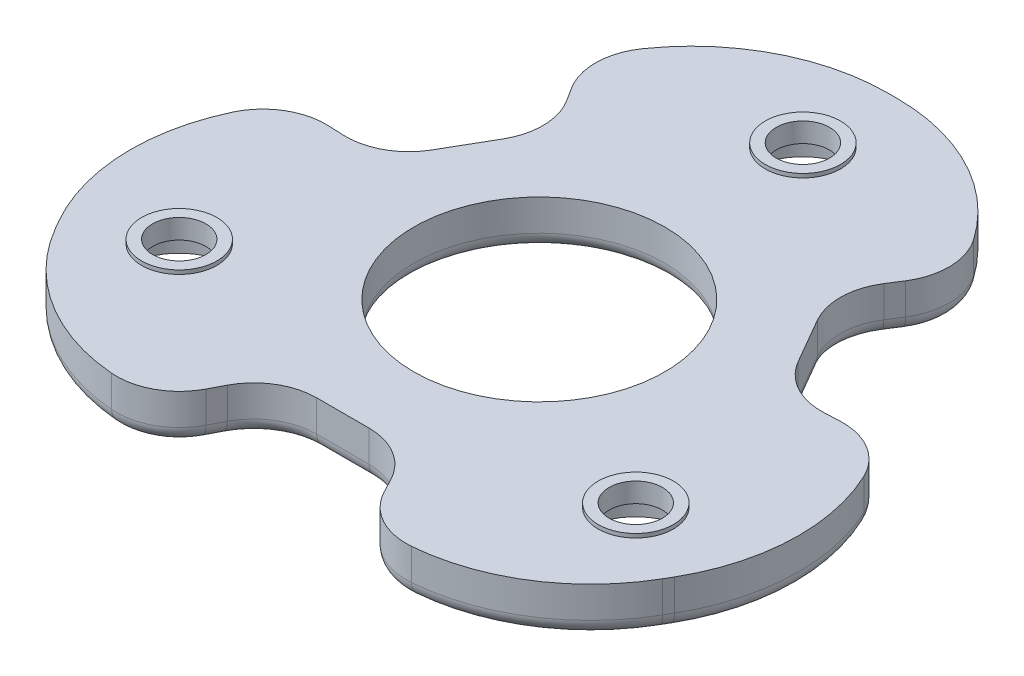
SolidWorks part; units mm, degrees
ref_plane "Front Plane" through (0, 0, 0) normal (0, 0, 1) x (1, 0, 0)
ref_plane "Top Plane" through (0, 0, 0) normal (0, 1, 0) x (1, 0, 0)
ref_plane "Right Plane" through (0, 0, 0) normal (1, 0, 0) x (0, 0, -1)
sketch "Sketch2" plane through (0, 0, 0) normal (0, 1, 0) x (1, 0, 0)
  line L0 (-0.2831, 22.5) -> (0.2831, 22.5)
  line L1 (11.1084, 16.25) -> (11.961, 14.7733)
  line L2 (19.6271, -11.0048) -> (19.344, -11.4952)
  line L3 (8.5187, -17.7452) -> (6.8136, -17.7452)
  line L4 (-19.344, -11.4952) -> (-19.6271, -11.0048)
  line L5 (-19.6271, 1.4952) -> (-18.7746, 2.9719)
  line L6 (-19.4856, -11.25) -> (0, 0) construction
  line L7 (0, 0) -> (0, 22.5) construction
  line L8 (0, 0) -> (19.4856, -11.25) construction
  line L9 (-11.961, 14.7733) -> (-8.8018, 9.8052)
  line L10 (-12.8925, 2.72) -> (-8.8018, 9.8052)
  line L11 (-12.8925, 2.72) -> (-18.7746, 2.9719)
  line L12 (-15.3678, 8.8726) -> (0, 0) construction
  line L13 (-15.8335, 2.8459) -> (-10.3814, 12.2893) construction
  line L14 (-11.961, 14.7733) -> (-11.1084, 16.25)
  line L15 (18.7746, 2.9719) -> (12.8925, 2.72)
  line L16 (8.8018, 9.8052) -> (12.8925, 2.72)
  line L17 (8.8018, 9.8052) -> (11.961, 14.7733)
  line L18 (-6.8136, -17.7452) -> (-4.0907, -12.5252)
  line L19 (4.0907, -12.5252) -> (-4.0907, -12.5252)
  line L20 (4.0907, -12.5252) -> (6.8136, -17.7452)
  line L21 (18.7746, 2.9719) -> (19.6271, 1.4952)
  line L22 (-6.8136, -17.7452) -> (-8.5187, -17.7452)
  circle A0 centre (0, 0) radius 8.4 construction
  circle A1 centre (0, 16.8) radius 8.4 construction
  circle A2 centre (0, 0) radius 24.8 construction
  circle A3 centre (0, 16.8) radius 1.7
  circle A4 centre (14.5492, -8.4) radius 1.7
  circle A5 centre (-14.5492, -8.4) radius 1.7
  arc A6 (19.6271, 1.4952) -> (19.6271, -11.0048) centre (8.8018, -4.7548) cw
  arc A7 (19.344, -11.4952) -> (8.5187, -17.7452) centre (8.5187, -5.2452) cw
  arc A8 (-8.5187, -17.7452) -> (-19.344, -11.4952) centre (-8.5187, -5.2452) cw
  arc A9 (-19.6271, -11.0048) -> (-19.6271, 1.4952) centre (-8.8018, -4.7548) cw
  arc A10 (0.2831, 22.5) -> (11.1084, 16.25) centre (0.2831, 10) cw
  arc A11 (-0.2831, 22.5) -> (-11.1084, 16.25) centre (-0.2831, 10) ccw
  circle A12 centre (0, 0) radius 8
  point P14 (0, 0)
  point P32 (7.5, 22.5)
  point P35 (-7.5, 22.5)
  point P42 (-13.1075, 7.5676)
  point P55 (0, 0)
  point P62 (0, 0)
  dimension "D1" = 16.8
  dimension "D2" = 16.8
  dimension "D3" = 49.6
  dimension "D4" = 3.4
  dimension "D9" = 12.5
  dimension "D10" = 16
  dimension "D6" = 120
  dimension "D7" = 15
  dimension "D8" = 22.5
  dimension "D11" = 3
  dimension "D5" = 3
extrude "Boss-Extrude1" add sketch "Sketch2" along normal blind 1
sketch "Sketch3" plane through (0, 0, 0) normal (0, -1, 0) x (1, 0, 0)
  line L6 (19.6271, 11.0048) -> (19.344, 11.4952)
  line L7 (8.5187, 17.7452) -> (6.8136, 17.7452)
  line L8 (-19.344, 11.4952) -> (-19.6271, 11.0048)
  line L9 (-19.6271, -1.4952) -> (-18.7746, -2.9719)
  line L10 (-0.2831, -22.5) -> (0.2831, -22.5)
  line L11 (11.1084, -16.25) -> (11.961, -14.7733)
  line L12 (19.6271, 11.0048) -> (19.344, 11.4952)
  line L13 (8.5187, 17.7452) -> (6.8136, 17.7452)
  line L14 (-19.344, 11.4952) -> (-19.6271, 11.0048)
  line L15 (-19.6271, -1.4952) -> (-18.7746, -2.9719)
  line L16 (-0.2831, -22.5) -> (0.2831, -22.5)
  line L17 (11.1084, -16.25) -> (11.961, -14.7733)
  line L30 (-11.961, -14.7733) -> (-11.1084, -16.25)
  line L31 (-11.961, -14.7733) -> (-11.1084, -16.25)
  line L32 (11.961, -14.7733) -> (8.8018, -9.8052)
  line L33 (11.961, -14.7733) -> (8.8018, -9.8052)
  line L34 (8.8018, -9.8052) -> (12.8925, -2.72)
  line L35 (8.8018, -9.8052) -> (12.8925, -2.72)
  line L36 (12.8925, -2.72) -> (18.7746, -2.9719)
  line L37 (12.8925, -2.72) -> (18.7746, -2.9719)
  line L38 (18.7746, -2.9719) -> (19.6271, -1.4952)
  line L39 (18.7746, -2.9719) -> (19.6271, -1.4952)
  line L40 (6.8136, 17.7452) -> (4.0907, 12.5252)
  line L41 (6.8136, 17.7452) -> (4.0907, 12.5252)
  line L42 (4.0907, 12.5252) -> (-4.0907, 12.5252)
  line L43 (4.0907, 12.5252) -> (-4.0907, 12.5252)
  line L44 (-4.0907, 12.5252) -> (-6.8136, 17.7452)
  line L45 (-4.0907, 12.5252) -> (-6.8136, 17.7452)
  line L46 (-6.8136, 17.7452) -> (-8.5187, 17.7452)
  line L47 (-6.8136, 17.7452) -> (-8.5187, 17.7452)
  line L48 (-18.7746, -2.9719) -> (-12.8925, -2.72)
  line L49 (-18.7746, -2.9719) -> (-12.8925, -2.72)
  line L50 (-12.8925, -2.72) -> (-8.8018, -9.8052)
  line L51 (-12.8925, -2.72) -> (-8.8018, -9.8052)
  line L52 (-8.8018, -9.8052) -> (-11.961, -14.7733)
  line L53 (-8.8018, -9.8052) -> (-11.961, -14.7733)
  circle A0 centre (-14.5492, 8.4) radius 3.5
  circle A1 centre (0, -16.8) radius 3.5
  circle A2 centre (14.5492, 8.4) radius 3.5
  circle A3 centre (0, 0) radius 8 construction
  circle A4 centre (0, 0) radius 8
  arc A6 (19.6271, -1.4952) -> (19.6271, 11.0048) centre (8.8018, 4.7548) ccw
  arc A7 (19.344, 11.4952) -> (8.5187, 17.7452) centre (8.5187, 5.2452) ccw
  arc A8 (-8.5187, 17.7452) -> (-19.344, 11.4952) centre (-8.5187, 5.2452) ccw
  arc A9 (-19.6271, 11.0048) -> (-19.6271, -1.4952) centre (-8.8018, 4.7548) ccw
  arc A10 (-11.1084, -16.25) -> (-0.2831, -22.5) centre (-0.2831, -10) ccw
  arc A11 (0.2831, -22.5) -> (11.1084, -16.25) centre (0.2831, -10) ccw
  arc A12 (19.6271, -1.4952) -> (19.6271, 11.0048) centre (8.8018, 4.7548) ccw
  arc A13 (19.344, 11.4952) -> (8.5187, 17.7452) centre (8.5187, 5.2452) ccw
  arc A14 (-8.5187, 17.7452) -> (-19.344, 11.4952) centre (-8.5187, 5.2452) ccw
  arc A15 (-19.6271, 11.0048) -> (-19.6271, -1.4952) centre (-8.8018, 4.7548) ccw
  arc A16 (-11.1084, -16.25) -> (-0.2831, -22.5) centre (-0.2831, -10) ccw
  arc A17 (0.2831, -22.5) -> (11.1084, -16.25) centre (0.2831, -10) ccw
  dimension "D2" = 7
  dimension "D1" = 0
extrude "Boss-Extrude2" add sketch "Sketch3" along normal blind 2
fillet "Fillet1" radius 4 12 edges at (-11.961, -0.5, -14.7733) (-8.8018, -0.5, -9.8052) (-18.7746, -0.5, -2.9719) (-12.8925, -0.5, -2.72) (-6.8136, -0.5, 17.7452) (-4.0907, -0.5, 12.5252) (6.8136, -0.5, 17.7452) (4.0907, -0.5, 12.5252) (18.7746, -0.5, -2.9719) (12.8925, -0.5, -2.72) (8.8018, -0.5, -9.8052) (11.961, -0.5, -14.7733)
fillet "Fillet2" radius 1 31 edges at (18.5592, -2, -2.2936) (15.817, -2, -2.8452) (13.2187, -2, -3.314) (10.8471, -2, -6.2626) (9.4793, -2, -9.7907) (10.3726, -2, -12.2753) (11.2659, -2, -14.9259) (6.0787, -2, -21.0753) (0, -2, -22.5) (-6.0787, -2, -21.0753) (-11.2659, -2, -14.9259) (-10.3726, -2, -12.2753) (-9.4793, -2, -9.7907) (-10.8471, -2, -6.2626) (-13.2187, -2, -3.314) (-15.817, -2, -2.8452) (-18.5592, -2, -2.2936) (-21.2911, -2, 5.2733) (-19.4856, -2, 11.25) (-15.2124, -2, 15.8019) (-7.2933, -2, 17.2195) (-5.4445, -2, 15.1206) (-3.7393, -2, 13.1047) (0, -2, 12.5252) (3.7393, -2, 13.1047) (5.4445, -2, 15.1206) (7.2933, -2, 17.2195) (15.2124, -2, 15.8019) (19.4856, -2, 11.25) (0, -2, -8) (21.2911, -2, 5.2733)
sketch "Sketch4" plane through (0, 1, 0) normal (0, 1, 0) x (1, 0, 0)
  circle A0 centre (0, 16.8) radius 2.4
  circle A1 centre (0, 16.8) radius 1.7 construction
  circle A2 centre (0, 16.8) radius 1.7
  circle A3 centre (14.5492, -8.4) radius 2.4
  circle A4 centre (14.5492, -8.4) radius 1.7
  circle A5 centre (-14.5492, -8.4) radius 2.4
  circle A6 centre (-14.5492, -8.4) radius 1.7
  point P14 (0, 0)
  dimension "D1" = 4.8
  dimension "D2" = 3
extrude "Boss-Extrude3" add sketch "Sketch4" along normal mid plane 0.5
